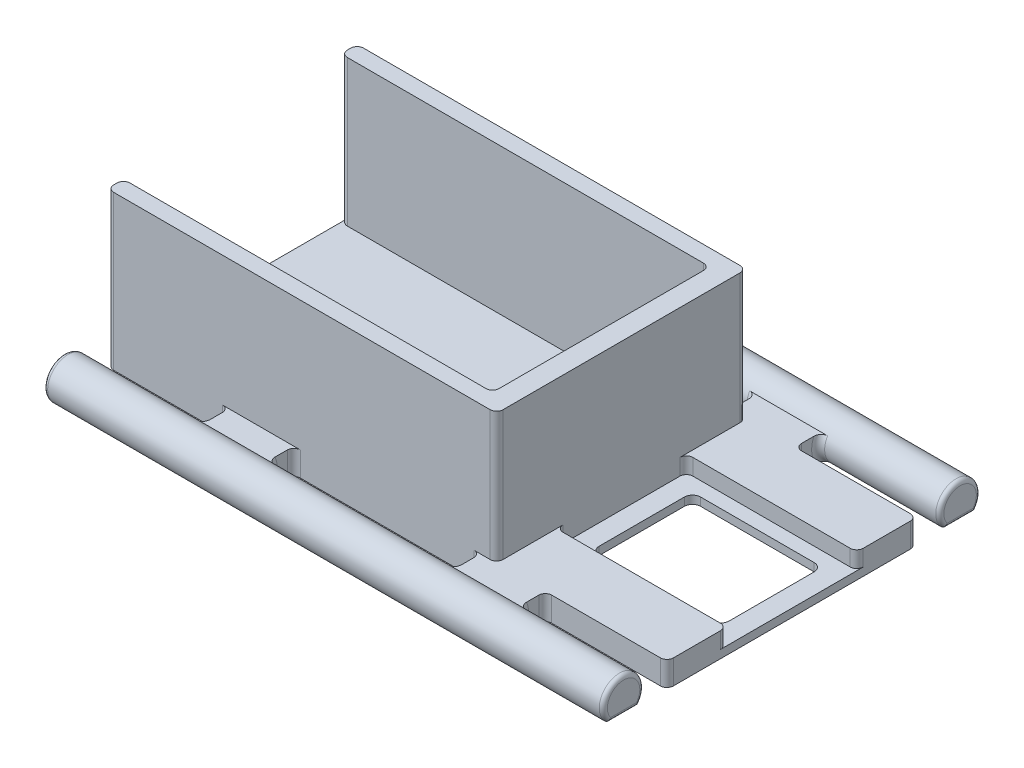
SolidWorks part; units mm, degrees
ref_plane "Front Plane" through (0, 0, 0) normal (0, 0, 1) x (1, 0, 0)
ref_plane "Top Plane" through (0, 0, 0) normal (0, 1, 0) x (1, 0, 0)
ref_plane "Right Plane" through (0, 0, 0) normal (1, 0, 0) x (0, 0, -1)
sketch "Sketch1" plane through (0, 0, 0) normal (0, 1, 0) x (1, 0, 0)
  line L1 (-31.8472, -9.5622) -> (37.1528, -9.5622)
  line L2 (-31.8472, -9.5622) -> (-31.8472, 21.2378)
  line L3 (-31.8472, 21.2378) -> (37.1528, 21.2378)
  line L4 (37.1528, -9.5622) -> (37.1528, 21.2378)
  dimension "D1" = 69
  dimension "D2" = 30.8
extrude "Boss-Extrude1" add sketch "Sketch1" along normal blind 19
sketch "Sketch2" plane through (-31.8472, 0, 0) normal (-1, 0, 0) x (0, 0, 1)
  line L0 (-21.2378, 19) -> (9.5622, 19) construction
  line L1 (-19.2378, 19) -> (7.5622, 19)
  line L2 (-19.2378, 19) -> (-19.2378, 1)
  line L3 (-19.2378, 1) -> (7.5622, 1)
  line L4 (7.5622, 19) -> (7.5622, 1)
  line L5 (-21.2378, 0) -> (9.5622, 0) construction
  point P8 (-5.8378, 0)
  point P9 (-5.8378, 1)
  dimension "D1" = 26.8
  dimension "D2" = 18
extrude "Cut-Extrude1" cut sketch "Sketch2" against normal blind 45.5
sketch "Sketch3" plane through (37.1528, 0, 0) normal (1, 0, 0) x (0, 0, -1)
  line L0 (24.7495, 0) -> (28.4156, 0)
  line L1 (-9.5622, 0) -> (21.2378, 0) construction
  line L2 (24.7495, 0) -> (21.2378, 0)
  line L3 (21.2378, 0) -> (21.2378, 3)
  line L4 (21.2378, 19) -> (21.2378, 0) construction
  line L5 (21.2378, 3) -> (24.4471, 3)
  line L6 (5.8378, 19) -> (5.8378, 0) construction
  line L7 (-9.5622, 19) -> (21.2378, 19) construction
  line L8 (-9.5622, 3) -> (-12.7715, 3)
  line L9 (-9.5622, 0) -> (-9.5622, 3)
  line L10 (-13.0739, 0) -> (-9.5622, 0)
  line L11 (-13.0739, 0) -> (-16.74, 0)
  circle A0 centre (26.5825, 1.7) radius 2.5
  arc A1 (28.4156, 0) -> (24.7495, 0) centre (26.5825, 1.7) cw
  arc A2 (24.7495, 0) -> (24.4471, 3) centre (26.5825, 1.7) cw
  arc A3 (-13.0739, 0) -> (-12.7715, 3) centre (-14.9069, 1.7) ccw
  arc A4 (-16.74, 0) -> (-13.0739, 0) centre (-14.9069, 1.7) ccw
  circle A5 centre (-14.9069, 1.7) radius 2.5
  point P4 (26.5825, 0)
  line M10 (21.2378, 0) -> (21.2378, 19)
  line M12 (-9.5622, 19) -> (-9.5622, 0)
  dimension "D1" = 5
  dimension "D2" = 1.7
  dimension "D3" = 1.3
extrude "Boss-Extrude2" add sketch "Sketch3" against normal through all separate body contours A0 L0 | A5 L11 A3 region at (37.1528, 1.9332, -26.5825) region at (37.1528, 1.9332, 14.9069)
extrude "Boss-Extrude3" add sketch "Sketch3<3>" against normal blind 8 from offset 15 contours A3 L10 L8 M12 | A0 L5 L2 M10 region at (37.1528, 1.4773, -22.7496) region at (37.1528, 1.4773, 11.074) offset against normal yes
sketch "Sketch3<3>" plane through (37.1528, 0, 0) normal (1, 0, 0) x (0, 0, -1) same geometry as "Sketch3"
extrude "Boss-Extrude4" add sketch "Sketch3<5>" along normal blind 8 from offset 54 contours A3 L10 L8 M12 | A0 L5 L2 M10 region at (37.1528, 1.4773, -22.7496) region at (37.1528, 1.4773, 11.074) offset against normal yes
sketch "Sketch3<5>" plane through (37.1528, 0, 0) normal (1, 0, 0) x (0, 0, -1) same geometry as "Sketch3"
sketch "Sketch4" plane through (0, 19, 0) normal (0, 1, 0) x (1, 0, 0)
  line L0 (37.1528, -9.5622) -> (37.1528, 21.2378) construction
  line L1 (37.1528, 13.8378) -> (16.1528, 13.8378)
  line L2 (37.1528, 13.8378) -> (37.1528, -2.1622)
  line L3 (37.1528, -2.1622) -> (16.1528, -2.1622)
  line L4 (16.1528, 13.8378) -> (16.1528, -2.1622)
  point P6 (37.1528, 5.8378)
  point P7 (37.1528, 5.8378)
  dimension "D1" = 16
  dimension "D2" = 21
extrude "Cut-Extrude2" cut sketch "Sketch4" against normal offset from surface (18 mm away) 1 up to face at (2.6528, 0, -5.8378)
sketch "Sketch5" plane through (0, 1, 0) normal (0, 1, 0) x (1, 0, 0)
  line L0 (37.1528, -2.1622) -> (37.1528, 13.8378) construction
  line L1 (34.6528, 12.0878) -> (18.6528, 12.0878)
  line L2 (34.6528, 12.0878) -> (34.6528, -0.4122)
  line L3 (34.6528, -0.4122) -> (18.6528, -0.4122)
  line L4 (18.6528, 12.0878) -> (18.6528, -0.4122)
  line L5 (16.1528, -2.1622) -> (37.1528, -2.1622) construction
  point P6 (37.1528, 5.8378)
  point P7 (34.6528, 5.8378)
  point P10 (26.6528, -2.1622)
  point P11 (26.6528, -0.4122)
  dimension "D1" = 12.5
  dimension "D2" = 16
extrude "Cut-Extrude3" cut sketch "Sketch5" against normal blind 1
fillet "Fillet1" radius 1 4 edges at (34.6528, 0.5, -12.0878) (34.6528, 0.5, 0.4122) (18.6528, 0.5, -12.0878) (18.6528, 0.5, 0.4122)
sketch "Sketch6" plane through (0, 19, 0) normal (0, 1, 0) x (1, 0, 0)
  line L0 (-31.8472, -9.5622) -> (37.1528, -9.5622) construction
  line L1 (37.1528, 21.2378) -> (16.1528, 21.2378)
  line L2 (37.1528, 21.2378) -> (37.1528, -9.5622)
  line L3 (37.1528, -9.5622) -> (16.1528, -9.5622)
  line L4 (16.1528, 21.2378) -> (16.1528, -9.5622)
  line L5 (16.1528, 13.8378) -> (16.1528, -2.1622) construction
extrude "Cut-Extrude4" cut sketch "Sketch6" against normal offset from surface (16 mm away) 2 up to face at (26.6528, 1, -5.8378)
fillet "Fillet2" radius 0.8 8 edges at (13.6528, 10, -19.2378) (13.6528, 10, 7.5622) (-31.8472, 10, 7.5622) (-31.8472, 10, -19.2378) (-31.8472, 9.5, -21.2378) (-31.8472, 9.5, 9.5622) (16.1528, 11, 9.5622) (16.1528, 11, -21.2378)
fillet "Fillet3" radius 0.8 22 edges at (-16.8472, 1.4493, -24.0951) (14.1528, 1.4493, -24.0951) (14.1528, 1.4493, 12.4195) (-16.8472, 1.4493, 12.4195) (-8.8472, 1.4493, 12.4195) (22.1528, 1.4493, 12.4195) (-8.8472, 1.4493, -24.0951) (22.1528, 1.4493, -24.0951) (37.1528, 1.5, 9.5622) (37.1528, 1.5, -21.2378) (37.1528, 2, 2.1622) (37.1528, 2, -13.8378) (16.1528, 2, -13.8378) (16.1528, 2, 2.1622) (22.1528, 1.5, 9.5622) (22.1528, 1.5, -21.2378) (14.1528, 1.5, -21.2378) (14.1528, 1.5, 9.5622) (-16.8472, 1.5, 9.5622) (-8.8472, 1.5, 9.5622) (-8.8472, 1.5, -21.2378) (-16.8472, 1.5, -21.2378)
fillet "Fillet4" radius 0.5 8 edges at (37.1528, 0, 14.9069) (37.1528, 4.2, 14.9069) (37.1528, 0, -26.5825) (37.1528, 4.2, -26.5825) (-31.8472, 0, 14.9069) (-31.8472, 4.2, 14.9069) (-31.8472, 0, -26.5825) (-31.8472, 4.2, -26.5825)
